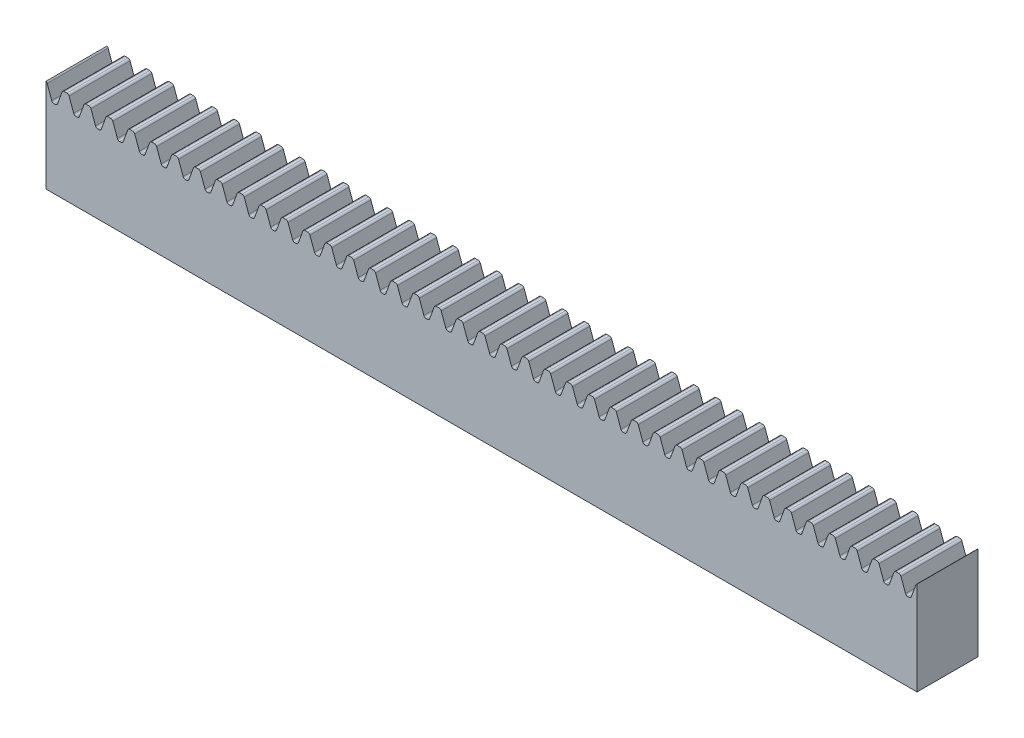
SolidWorks part; units mm, degrees
ref_plane "Front Plane" through (0, 0, 0) normal (0, 0, 1) x (1, 0, 0)
ref_plane "Top Plane" through (0, 0, 0) normal (0, 1, 0) x (1, 0, 0)
ref_plane "Right Plane" through (0, 0, 0) normal (1, 0, 0) x (0, 0, -1)
sketch "Sketch1" plane through (0, 0, 0) normal (0, 0, 1) x (1, 0, 0)
  line L0 (-50, 6.15) -> (-50, -6.15) construction
  line L1 (-50, -6.15) -> (50, -6.15) construction
  line L2 (50, -6.15) -> (50, 6.15) construction
  line L4 (0, 6.15) -> (0, -6.15) construction
  line L5 (-50, 5.35) -> (50, 5.35) construction
  line L6 (-48.0894, 6.15) -> (-47.4151, 6.15) construction
  line L7 (-47.4151, 6.15) -> (-46.7599, 4.35) construction
  line L8 (-48.0894, 6.15) -> (-48.7445, 4.35) construction
  line L9 (-48.7445, 4.35) -> (-46.7599, 4.35) construction
  line L10 (-47.7522, 6.15) -> (-47.7522, 4.35) construction
  line L11 (-50, 0) -> (-42.7257, 0) construction
  line L12 (50, 0) -> (42.7257, 0) construction
  point P15 (-45.2389, 6.15)
  point P16 (-19.5, -6.15)
  point P17 (-47.1239, 5.35)
  point P18 (-48.3805, 5.35)
  point P21 (-0.4, -6.15)
  dimension "Length" = 100
  dimension "Height" = 12.3
  dimension "Approximate Number of Teeth" = 39
  dimension "Pressure Angle" = 20
  dimension "Circular Pitch" = 2.5133
  dimension "Addendum" = 0.8
  dimension "Dedendum" = 1
  dimension "Circular Tooth Thickness" = 1.2566
  dimension "Module" = 0.8
  dimension "Rack Length" = 95.5044
  dimension "D1" = 5.0265
sketch "Sketch2" plane through (0, 0, 0) normal (1, 0, 0) x (0, 0, -1)
  line L0 (-4, 0) -> (4, 0) construction
  dimension "Face Width" = 8
sketch "Sketch3" plane through (0, 0, 0) normal (0, 0, 1) x (1, 0, 0)
  line L1 (-50, 6.15) -> (50, 6.15)
  line L2 (-50, 6.15) -> (-50, -6.15)
  line L3 (-50, -6.15) -> (50, -6.15)
  line L4 (50, 6.15) -> (50, -6.15)
extrude "Boss-Extrude1" add sketch "Sketch3" against normal up to vertex (4 mm away) and the other way up to vertex (4 mm away) up to point (0, 0, -4) other way up to point (0, 0, 4)
sketch "Sketch4" plane through (0, 0, 0) normal (0, 0, 1) x (1, 0, 0)
  line L0 (-47.7522, 6.15) -> (-45.2389, 6.15) construction
  line L9 (-46.4956, 6.15) -> (-46.4956, 4.35)
  line L10 (-46.4956, 4.35) -> (-46.7599, 4.35)
  line L11 (-46.7599, 4.35) -> (-47.4151, 6.15)
  line L12 (-47.4151, 6.15) -> (-46.4956, 6.15)
  line L13 (-48.0894, 6.15) -> (-48.7445, 4.35)
  line L14 (-48.7445, 4.35) -> (-49.0088, 4.35)
  line L15 (-49.0088, 4.35) -> (-49.0088, 6.15)
  line L16 (-49.0088, 6.15) -> (-48.0894, 6.15)
  line L17 (50, 6.15) -> (-50, 6.15) construction
  line L18 (-48.0894, 6.15) -> (-47.9014, 6.15)
  line L19 (-47.603, 6.15) -> (-47.4151, 6.15)
  arc A0 (-48.9324, 4.35) -> (-48.6802, 4.5266) centre (-48.9324, 4.6184) ccw
  arc A1 (-46.8242, 4.5266) -> (-46.572, 4.35) centre (-46.572, 4.6184) ccw
  arc A2 (-48.1536, 5.9734) -> (-47.9014, 6.15) centre (-47.9014, 5.8816) cw
  arc A3 (-47.603, 6.15) -> (-47.3508, 5.9734) centre (-47.603, 5.8816) cw
  dimension "D1" = 0.2684
extrude "Cut-Extrude1" cut sketch "Sketch4" against normal through all both and the other way through all contours L14 A0 L13 L16 L15 | L13 A2 L18 | L19 A3 L11 | L11 A1 L10 L9 L12 region at (-46.8223, 5.4223, 0) region at (-47.4415, 6.1123, 0) region at (-48.0629, 6.1123, 0) region at (-48.6821, 5.4223, 0)
pattern_linear "LPattern1" count 40 spacing 2.5133 along (1, 0, 0) count 2 spacing 2.5133 along (-1, 0, 0) of "Cut-Extrude1"
sketch "Drawing Refernce 1" plane through (0, 0, 4) normal (0, 0, 1) x (1, 0, 0)
  line L0 (-50, 0) -> (50, 0) construction
  point P6 (-35, 0)
  point P7 (-27.5, 0)
  point P8 (35, 0)
  dimension "D1" = 15
  dimension "D2" = 22.5
  dimension "D3" = 15
sketch "Sketch5" plane through (0, -6.15, 0) normal (0, -1, 0) x (1, 0, 0)
  line L1 (-50, 4) -> (50, 4)
  line L2 (-50, 4) -> (-50, -4)
  line L3 (-50, -4) -> (50, -4)
  line L4 (50, 4) -> (50, -4)
extrude "Cut-Extrude2" cut sketch "Sketch5" against normal blind 1.55
sketch "Sketch6" plane through (0, 0, -4) normal (0, 0, -1) x (-1, 0, 0)
  line L162 (-50, -4.6) -> (50, -4.6)
  line L163 (50, -4.6) -> (50, 6.1235)
  line L164 (49.8641, 5.9734) -> (49.3375, 4.5266)
  line L165 (49.0853, 4.35) -> (48.9324, 4.35)
  line L166 (48.6802, 4.5266) -> (48.1536, 5.9734)
  line L167 (47.9014, 6.15) -> (47.603, 6.15)
  line L168 (47.3508, 5.9734) -> (46.8242, 4.5266)
  line L169 (46.572, 4.35) -> (46.4192, 4.35)
  line L170 (46.1669, 4.5266) -> (45.6404, 5.9734)
  line L171 (45.3881, 6.15) -> (45.0897, 6.15)
  line L172 (44.8375, 5.9734) -> (44.3109, 4.5266)
  line L173 (44.0587, 4.35) -> (43.9059, 4.35)
  line L174 (43.6537, 4.5266) -> (43.1271, 5.9734)
  line L175 (42.8749, 6.15) -> (42.5765, 6.15)
  line L176 (42.3242, 5.9734) -> (41.7977, 4.5266)
  line L177 (41.5454, 4.35) -> (41.3926, 4.35)
  line L178 (41.1404, 4.5266) -> (40.6138, 5.9734)
  line L179 (40.3616, 6.15) -> (40.0632, 6.15)
  line L180 (39.811, 5.9734) -> (39.2844, 4.5266)
  line L181 (39.0322, 4.35) -> (38.8793, 4.35)
  line L182 (38.6271, 4.5266) -> (38.1005, 5.9734)
  line L183 (37.8483, 6.15) -> (37.5499, 6.15)
  line L184 (37.2977, 5.9734) -> (36.7711, 4.5266)
  line L185 (36.5189, 4.35) -> (36.3661, 4.35)
  line L186 (36.1138, 4.5266) -> (35.5873, 5.9734)
  line L187 (35.335, 6.15) -> (35.0366, 6.15)
  line L188 (34.7844, 5.9734) -> (34.2578, 4.5266)
  line L189 (34.0056, 4.35) -> (33.8528, 4.35)
  line L190 (33.6006, 4.5266) -> (33.074, 5.9734)
  line L191 (32.8218, 6.15) -> (32.5234, 6.15)
  line L192 (32.2711, 5.9734) -> (31.7446, 4.5266)
  line L193 (31.4923, 4.35) -> (31.3395, 4.35)
  line L194 (31.0873, 4.5266) -> (30.5607, 5.9734)
  line L195 (30.3085, 6.15) -> (30.0101, 6.15)
  line L196 (29.7579, 5.9734) -> (29.2313, 4.5266)
  line L197 (28.9791, 4.35) -> (28.8262, 4.35)
  line L198 (28.574, 4.5266) -> (28.0474, 5.9734)
  line L199 (27.7952, 6.15) -> (27.4968, 6.15)
  line L200 (27.2446, 5.9734) -> (26.718, 4.5266)
  line L201 (26.4658, 4.35) -> (26.313, 4.35)
  line L202 (26.0608, 4.5266) -> (25.5342, 5.9734)
  line L203 (25.2819, 6.15) -> (24.9835, 6.15)
  line L204 (24.7313, 5.9734) -> (24.2047, 4.5266)
  line L205 (23.9525, 4.35) -> (23.7997, 4.35)
  line L206 (23.5475, 4.5266) -> (23.0209, 5.9734)
  line L207 (22.7687, 6.15) -> (22.4703, 6.15)
  line L208 (22.218, 5.9734) -> (21.6915, 4.5266)
  line L209 (21.4392, 4.35) -> (21.2864, 4.35)
  line L210 (21.0342, 4.5266) -> (20.5076, 5.9734)
  line L211 (20.2554, 6.15) -> (19.957, 6.15)
  line L212 (19.7048, 5.9734) -> (19.1782, 4.5266)
  line L213 (18.926, 4.35) -> (18.7731, 4.35)
  line L214 (18.5209, 4.5266) -> (17.9943, 5.9734)
  line L215 (17.7421, 6.15) -> (17.4437, 6.15)
  line L216 (17.1915, 5.9734) -> (16.6649, 4.5266)
  line L217 (16.4127, 4.35) -> (16.2599, 4.35)
  line L218 (16.0077, 4.5266) -> (15.4811, 5.9734)
  line L219 (15.2288, 6.15) -> (14.9304, 6.15)
  line L220 (14.6782, 5.9734) -> (14.1516, 4.5266)
  line L221 (13.8994, 4.35) -> (13.7466, 4.35)
  line L222 (13.4944, 4.5266) -> (12.9678, 5.9734)
  line L223 (12.7156, 6.15) -> (12.4172, 6.15)
  line L224 (12.1649, 5.9734) -> (11.6384, 4.5266)
  line L225 (11.3861, 4.35) -> (11.2333, 4.35)
  line L226 (10.9811, 4.5266) -> (10.4545, 5.9734)
  line L227 (10.2023, 6.15) -> (9.9039, 6.15)
  line L228 (9.6517, 5.9734) -> (9.1251, 4.5266)
  line L229 (8.8729, 4.35) -> (8.72, 4.35)
  line L230 (8.4678, 4.5266) -> (7.9412, 5.9734)
  line L231 (7.689, 6.15) -> (7.3906, 6.15)
  line L232 (7.1384, 5.9734) -> (6.6118, 4.5266)
  line L233 (6.3596, 4.35) -> (6.2068, 4.35)
  line L234 (5.9546, 4.5266) -> (5.428, 5.9734)
  line L235 (5.1758, 6.15) -> (4.8773, 6.15)
  line L236 (4.6251, 5.9734) -> (4.0985, 4.5266)
  line L237 (3.8463, 4.35) -> (3.6935, 4.35)
  line L238 (3.4413, 4.5266) -> (2.9147, 5.9734)
  line L239 (2.6625, 6.15) -> (2.3641, 6.15)
  line L240 (2.1119, 5.9734) -> (1.5853, 4.5266)
  line L241 (1.333, 4.35) -> (1.1802, 4.35)
  line L242 (0.928, 4.5266) -> (0.4014, 5.9734)
  line L243 (0.1492, 6.15) -> (-0.1492, 6.15)
  line L244 (-0.4014, 5.9734) -> (-0.928, 4.5266)
  line L245 (-1.1802, 4.35) -> (-1.333, 4.35)
  line L246 (-1.5853, 4.5266) -> (-2.1119, 5.9734)
  line L247 (-2.3641, 6.15) -> (-2.6625, 6.15)
  line L248 (-2.9147, 5.9734) -> (-3.4413, 4.5266)
  line L249 (-3.6935, 4.35) -> (-3.8463, 4.35)
  line L250 (-4.0985, 4.5266) -> (-4.6251, 5.9734)
  line L251 (-4.8773, 6.15) -> (-5.1758, 6.15)
  line L252 (-5.428, 5.9734) -> (-5.9546, 4.5266)
  line L253 (-6.2068, 4.35) -> (-6.3596, 4.35)
  line L254 (-6.6118, 4.5266) -> (-7.1384, 5.9734)
  line L255 (-7.3906, 6.15) -> (-7.689, 6.15)
  line L256 (-7.9412, 5.9734) -> (-8.4678, 4.5266)
  line L257 (-8.72, 4.35) -> (-8.8729, 4.35)
  line L258 (-9.1251, 4.5266) -> (-9.6517, 5.9734)
  line L259 (-9.9039, 6.15) -> (-10.2023, 6.15)
  line L260 (-10.4545, 5.9734) -> (-10.9811, 4.5266)
  line L261 (-11.2333, 4.35) -> (-11.3861, 4.35)
  line L262 (-11.6384, 4.5266) -> (-12.1649, 5.9734)
  line L263 (-12.4172, 6.15) -> (-12.7156, 6.15)
  line L264 (-12.9678, 5.9734) -> (-13.4944, 4.5266)
  line L265 (-13.7466, 4.35) -> (-13.8994, 4.35)
  line L266 (-14.1516, 4.5266) -> (-14.6782, 5.9734)
  line L267 (-14.9304, 6.15) -> (-15.2288, 6.15)
  line L268 (-15.4811, 5.9734) -> (-16.0077, 4.5266)
  line L269 (-16.2599, 4.35) -> (-16.4127, 4.35)
  line L270 (-16.6649, 4.5266) -> (-17.1915, 5.9734)
  line L271 (-17.4437, 6.15) -> (-17.7421, 6.15)
  line L272 (-17.9943, 5.9734) -> (-18.5209, 4.5266)
  line L273 (-18.7731, 4.35) -> (-18.926, 4.35)
  line L274 (-19.1782, 4.5266) -> (-19.7048, 5.9734)
  line L275 (-19.957, 6.15) -> (-20.2554, 6.15)
  line L276 (-20.5076, 5.9734) -> (-21.0342, 4.5266)
  line L277 (-21.2864, 4.35) -> (-21.4392, 4.35)
  line L278 (-21.6915, 4.5266) -> (-22.218, 5.9734)
  line L279 (-22.4703, 6.15) -> (-22.7687, 6.15)
  line L280 (-23.0209, 5.9734) -> (-23.5475, 4.5266)
  line L281 (-23.7997, 4.35) -> (-23.9525, 4.35)
  line L282 (-24.2047, 4.5266) -> (-24.7313, 5.9734)
  line L283 (-24.9835, 6.15) -> (-25.2819, 6.15)
  line L284 (-25.5342, 5.9734) -> (-26.0608, 4.5266)
  line L285 (-26.313, 4.35) -> (-26.4658, 4.35)
  line L286 (-26.718, 4.5266) -> (-27.2446, 5.9734)
  line L287 (-27.4968, 6.15) -> (-27.7952, 6.15)
  line L288 (-28.0474, 5.9734) -> (-28.574, 4.5266)
  line L289 (-28.8262, 4.35) -> (-28.9791, 4.35)
  line L290 (-29.2313, 4.5266) -> (-29.7579, 5.9734)
  line L291 (-30.0101, 6.15) -> (-30.3085, 6.15)
  line L292 (-30.5607, 5.9734) -> (-31.0873, 4.5266)
  line L293 (-31.3395, 4.35) -> (-31.4923, 4.35)
  line L294 (-31.7446, 4.5266) -> (-32.2711, 5.9734)
  line L295 (-32.5234, 6.15) -> (-32.8218, 6.15)
  line L296 (-33.074, 5.9734) -> (-33.6006, 4.5266)
  line L297 (-33.8528, 4.35) -> (-34.0056, 4.35)
  line L298 (-34.2578, 4.5266) -> (-34.7844, 5.9734)
  line L299 (-35.0366, 6.15) -> (-35.335, 6.15)
  line L300 (-35.5873, 5.9734) -> (-36.1138, 4.5266)
  line L301 (-36.3661, 4.35) -> (-36.5189, 4.35)
  line L302 (-36.7711, 4.5266) -> (-37.2977, 5.9734)
  line L303 (-37.5499, 6.15) -> (-37.8483, 6.15)
  line L304 (-38.1005, 5.9734) -> (-38.6271, 4.5266)
  line L305 (-38.8793, 4.35) -> (-39.0322, 4.35)
  line L306 (-39.2844, 4.5266) -> (-39.811, 5.9734)
  line L307 (-40.0632, 6.15) -> (-40.3616, 6.15)
  line L308 (-40.6138, 5.9734) -> (-41.1404, 4.5266)
  line L309 (-41.3926, 4.35) -> (-41.5454, 4.35)
  line L310 (-41.7977, 4.5266) -> (-42.3242, 5.9734)
  line L311 (-42.5765, 6.15) -> (-42.8749, 6.15)
  line L312 (-43.1271, 5.9734) -> (-43.6537, 4.5266)
  line L313 (-43.9059, 4.35) -> (-44.0587, 4.35)
  line L314 (-44.3109, 4.5266) -> (-44.8375, 5.9734)
  line L315 (-45.0897, 6.15) -> (-45.3881, 6.15)
  line L316 (-45.6404, 5.9734) -> (-46.1669, 4.5266)
  line L317 (-46.4192, 4.35) -> (-46.572, 4.35)
  line L318 (-46.8242, 4.5266) -> (-47.3508, 5.9734)
  line L319 (-47.603, 6.15) -> (-47.9014, 6.15)
  line L320 (-48.1536, 5.9734) -> (-48.6802, 4.5266)
  line L321 (-48.9324, 4.35) -> (-49.0853, 4.35)
  line L322 (-49.3375, 4.5266) -> (-49.8641, 5.9734)
  line L323 (-50, 6.1235) -> (-50, -4.6)
  line L325 (50, -4.6) -> (50, 6.1235)
  line L326 (49.8641, 5.9734) -> (49.3375, 4.5266)
  line L327 (49.0853, 4.35) -> (48.9324, 4.35)
  line L328 (48.6802, 4.5266) -> (48.1536, 5.9734)
  line L329 (47.9014, 6.15) -> (47.603, 6.15)
  line L330 (47.3508, 5.9734) -> (46.8242, 4.5266)
  line L331 (46.572, 4.35) -> (46.4192, 4.35)
  line L332 (46.1669, 4.5266) -> (45.6404, 5.9734)
  line L333 (45.3881, 6.15) -> (45.0897, 6.15)
  line L334 (44.8375, 5.9734) -> (44.3109, 4.5266)
  line L335 (44.0587, 4.35) -> (43.9059, 4.35)
  line L336 (43.6537, 4.5266) -> (43.1271, 5.9734)
  line L337 (42.8749, 6.15) -> (42.5765, 6.15)
  line L338 (42.3242, 5.9734) -> (41.7977, 4.5266)
  line L339 (41.5454, 4.35) -> (41.3926, 4.35)
  line L340 (41.1404, 4.5266) -> (40.6138, 5.9734)
  line L341 (40.3616, 6.15) -> (40.0632, 6.15)
  line L342 (39.811, 5.9734) -> (39.2844, 4.5266)
  line L343 (39.0322, 4.35) -> (38.8793, 4.35)
  line L344 (38.6271, 4.5266) -> (38.1005, 5.9734)
  line L345 (37.8483, 6.15) -> (37.5499, 6.15)
  line L346 (37.2977, 5.9734) -> (36.7711, 4.5266)
  line L347 (36.5189, 4.35) -> (36.3661, 4.35)
  line L348 (36.1138, 4.5266) -> (35.5873, 5.9734)
  line L349 (35.335, 6.15) -> (35.0366, 6.15)
  line L350 (34.7844, 5.9734) -> (34.2578, 4.5266)
  line L351 (34.0056, 4.35) -> (33.8528, 4.35)
  line L352 (33.6006, 4.5266) -> (33.074, 5.9734)
  line L353 (32.8218, 6.15) -> (32.5234, 6.15)
  line L354 (32.2711, 5.9734) -> (31.7446, 4.5266)
  line L355 (31.4923, 4.35) -> (31.3395, 4.35)
  line L356 (31.0873, 4.5266) -> (30.5607, 5.9734)
  line L357 (30.3085, 6.15) -> (30.0101, 6.15)
  line L358 (29.7579, 5.9734) -> (29.2313, 4.5266)
  line L359 (28.9791, 4.35) -> (28.8262, 4.35)
  line L360 (28.574, 4.5266) -> (28.0474, 5.9734)
  line L361 (27.7952, 6.15) -> (27.4968, 6.15)
  line L362 (27.2446, 5.9734) -> (26.718, 4.5266)
  line L363 (26.4658, 4.35) -> (26.313, 4.35)
  line L364 (26.0608, 4.5266) -> (25.5342, 5.9734)
  line L365 (25.2819, 6.15) -> (24.9835, 6.15)
  line L366 (24.7313, 5.9734) -> (24.2047, 4.5266)
  line L367 (23.9525, 4.35) -> (23.7997, 4.35)
  line L368 (23.5475, 4.5266) -> (23.0209, 5.9734)
  line L369 (22.7687, 6.15) -> (22.4703, 6.15)
  line L370 (22.218, 5.9734) -> (21.6915, 4.5266)
  line L371 (21.4392, 4.35) -> (21.2864, 4.35)
  line L372 (21.0342, 4.5266) -> (20.5076, 5.9734)
  line L373 (20.2554, 6.15) -> (19.957, 6.15)
  line L374 (19.7048, 5.9734) -> (19.1782, 4.5266)
  line L375 (18.926, 4.35) -> (18.7731, 4.35)
  line L376 (18.5209, 4.5266) -> (17.9943, 5.9734)
  line L377 (17.7421, 6.15) -> (17.4437, 6.15)
  line L378 (17.1915, 5.9734) -> (16.6649, 4.5266)
  line L379 (16.4127, 4.35) -> (16.2599, 4.35)
  line L380 (16.0077, 4.5266) -> (15.4811, 5.9734)
  line L381 (15.2288, 6.15) -> (14.9304, 6.15)
  line L382 (14.6782, 5.9734) -> (14.1516, 4.5266)
  line L383 (13.8994, 4.35) -> (13.7466, 4.35)
  line L384 (13.4944, 4.5266) -> (12.9678, 5.9734)
  line L385 (12.7156, 6.15) -> (12.4172, 6.15)
  line L386 (12.1649, 5.9734) -> (11.6384, 4.5266)
  line L387 (11.3861, 4.35) -> (11.2333, 4.35)
  line L388 (10.9811, 4.5266) -> (10.4545, 5.9734)
  line L389 (10.2023, 6.15) -> (9.9039, 6.15)
  line L390 (9.6517, 5.9734) -> (9.1251, 4.5266)
  line L391 (8.8729, 4.35) -> (8.72, 4.35)
  line L392 (8.4678, 4.5266) -> (7.9412, 5.9734)
  line L393 (7.689, 6.15) -> (7.3906, 6.15)
  line L394 (7.1384, 5.9734) -> (6.6118, 4.5266)
  line L395 (6.3596, 4.35) -> (6.2068, 4.35)
  line L396 (5.9546, 4.5266) -> (5.428, 5.9734)
  line L397 (5.1758, 6.15) -> (4.8773, 6.15)
  line L398 (4.6251, 5.9734) -> (4.0985, 4.5266)
  line L399 (3.8463, 4.35) -> (3.6935, 4.35)
  line L400 (3.4413, 4.5266) -> (2.9147, 5.9734)
  line L401 (2.6625, 6.15) -> (2.3641, 6.15)
  line L402 (2.1119, 5.9734) -> (1.5853, 4.5266)
  line L403 (1.333, 4.35) -> (1.1802, 4.35)
  line L404 (0.928, 4.5266) -> (0.4014, 5.9734)
  line L405 (0.1492, 6.15) -> (-0.1492, 6.15)
  line L406 (-0.4014, 5.9734) -> (-0.928, 4.5266)
  line L407 (-1.1802, 4.35) -> (-1.333, 4.35)
  line L408 (-1.5853, 4.5266) -> (-2.1119, 5.9734)
  line L409 (-2.3641, 6.15) -> (-2.6625, 6.15)
  line L410 (-2.9147, 5.9734) -> (-3.4413, 4.5266)
  line L411 (-3.6935, 4.35) -> (-3.8463, 4.35)
  line L412 (-4.0985, 4.5266) -> (-4.6251, 5.9734)
  line L413 (-4.8773, 6.15) -> (-5.1758, 6.15)
  line L414 (-5.428, 5.9734) -> (-5.9546, 4.5266)
  line L415 (-6.2068, 4.35) -> (-6.3596, 4.35)
  line L416 (-6.6118, 4.5266) -> (-7.1384, 5.9734)
  line L417 (-7.3906, 6.15) -> (-7.689, 6.15)
  line L418 (-7.9412, 5.9734) -> (-8.4678, 4.5266)
  line L419 (-8.72, 4.35) -> (-8.8729, 4.35)
  line L420 (-9.1251, 4.5266) -> (-9.6517, 5.9734)
  line L421 (-9.9039, 6.15) -> (-10.2023, 6.15)
  line L422 (-10.4545, 5.9734) -> (-10.9811, 4.5266)
  line L423 (-11.2333, 4.35) -> (-11.3861, 4.35)
  line L424 (-11.6384, 4.5266) -> (-12.1649, 5.9734)
  line L425 (-12.4172, 6.15) -> (-12.7156, 6.15)
  line L426 (-12.9678, 5.9734) -> (-13.4944, 4.5266)
  line L427 (-13.7466, 4.35) -> (-13.8994, 4.35)
  line L428 (-14.1516, 4.5266) -> (-14.6782, 5.9734)
  line L429 (-14.9304, 6.15) -> (-15.2288, 6.15)
  line L430 (-15.4811, 5.9734) -> (-16.0077, 4.5266)
  line L431 (-16.2599, 4.35) -> (-16.4127, 4.35)
  line L432 (-16.6649, 4.5266) -> (-17.1915, 5.9734)
  line L433 (-17.4437, 6.15) -> (-17.7421, 6.15)
  line L434 (-17.9943, 5.9734) -> (-18.5209, 4.5266)
  line L435 (-18.7731, 4.35) -> (-18.926, 4.35)
  line L436 (-19.1782, 4.5266) -> (-19.7048, 5.9734)
  line L437 (-19.957, 6.15) -> (-20.2554, 6.15)
  line L438 (-20.5076, 5.9734) -> (-21.0342, 4.5266)
  line L439 (-21.2864, 4.35) -> (-21.4392, 4.35)
  line L440 (-21.6915, 4.5266) -> (-22.218, 5.9734)
  line L441 (-22.4703, 6.15) -> (-22.7687, 6.15)
  line L442 (-23.0209, 5.9734) -> (-23.5475, 4.5266)
  line L443 (-23.7997, 4.35) -> (-23.9525, 4.35)
  line L444 (-24.2047, 4.5266) -> (-24.7313, 5.9734)
  line L445 (-24.9835, 6.15) -> (-25.2819, 6.15)
  line L446 (-25.5342, 5.9734) -> (-26.0608, 4.5266)
  line L447 (-26.313, 4.35) -> (-26.4658, 4.35)
  line L448 (-26.718, 4.5266) -> (-27.2446, 5.9734)
  line L449 (-27.4968, 6.15) -> (-27.7952, 6.15)
  line L450 (-28.0474, 5.9734) -> (-28.574, 4.5266)
  line L451 (-28.8262, 4.35) -> (-28.9791, 4.35)
  line L452 (-29.2313, 4.5266) -> (-29.7579, 5.9734)
  line L453 (-30.0101, 6.15) -> (-30.3085, 6.15)
  line L454 (-30.5607, 5.9734) -> (-31.0873, 4.5266)
  line L455 (-31.3395, 4.35) -> (-31.4923, 4.35)
  line L456 (-31.7446, 4.5266) -> (-32.2711, 5.9734)
  line L457 (-32.5234, 6.15) -> (-32.8218, 6.15)
  line L458 (-33.074, 5.9734) -> (-33.6006, 4.5266)
  line L459 (-33.8528, 4.35) -> (-34.0056, 4.35)
  line L460 (-34.2578, 4.5266) -> (-34.7844, 5.9734)
  line L461 (-35.0366, 6.15) -> (-35.335, 6.15)
  line L462 (-35.5873, 5.9734) -> (-36.1138, 4.5266)
  line L463 (-36.3661, 4.35) -> (-36.5189, 4.35)
  line L464 (-36.7711, 4.5266) -> (-37.2977, 5.9734)
  line L465 (-37.5499, 6.15) -> (-37.8483, 6.15)
  line L466 (-38.1005, 5.9734) -> (-38.6271, 4.5266)
  line L467 (-38.8793, 4.35) -> (-39.0322, 4.35)
  line L468 (-39.2844, 4.5266) -> (-39.811, 5.9734)
  line L469 (-40.0632, 6.15) -> (-40.3616, 6.15)
  line L470 (-40.6138, 5.9734) -> (-41.1404, 4.5266)
  line L471 (-41.3926, 4.35) -> (-41.5454, 4.35)
  line L472 (-41.7977, 4.5266) -> (-42.3242, 5.9734)
  line L473 (-42.5765, 6.15) -> (-42.8749, 6.15)
  line L474 (-43.1271, 5.9734) -> (-43.6537, 4.5266)
  line L475 (-43.9059, 4.35) -> (-44.0587, 4.35)
  line L476 (-44.3109, 4.5266) -> (-44.8375, 5.9734)
  line L477 (-45.0897, 6.15) -> (-45.3881, 6.15)
  line L478 (-45.6404, 5.9734) -> (-46.1669, 4.5266)
  line L479 (-46.4192, 4.35) -> (-46.572, 4.35)
  line L480 (-46.8242, 4.5266) -> (-47.3508, 5.9734)
  line L481 (-47.603, 6.15) -> (-47.9014, 6.15)
  line L482 (-48.1536, 5.9734) -> (-48.6802, 4.5266)
  line L483 (-48.9324, 4.35) -> (-49.0853, 4.35)
  line L484 (-49.3375, 4.5266) -> (-49.8641, 5.9734)
  line L485 (-50, 6.1235) -> (-50, -4.6)
  line L487 (-50, -4.6) -> (50, -4.6)
  arc A160 (50, 6.1235) -> (49.8641, 5.9734) centre (50.1163, 5.8816) ccw
  arc A161 (49.0853, 4.35) -> (49.3375, 4.5266) centre (49.0853, 4.6184) ccw
  arc A162 (48.6802, 4.5266) -> (48.9324, 4.35) centre (48.9324, 4.6184) ccw
  arc A163 (48.1536, 5.9734) -> (47.9014, 6.15) centre (47.9014, 5.8816) ccw
  arc A164 (47.603, 6.15) -> (47.3508, 5.9734) centre (47.603, 5.8816) ccw
  arc A165 (46.572, 4.35) -> (46.8242, 4.5266) centre (46.572, 4.6184) ccw
  arc A166 (46.1669, 4.5266) -> (46.4192, 4.35) centre (46.4192, 4.6184) ccw
  arc A167 (45.6404, 5.9734) -> (45.3881, 6.15) centre (45.3881, 5.8816) ccw
  arc A168 (45.0897, 6.15) -> (44.8375, 5.9734) centre (45.0897, 5.8816) ccw
  arc A169 (44.0587, 4.35) -> (44.3109, 4.5266) centre (44.0587, 4.6184) ccw
  arc A170 (43.6537, 4.5266) -> (43.9059, 4.35) centre (43.9059, 4.6184) ccw
  arc A171 (43.1271, 5.9734) -> (42.8749, 6.15) centre (42.8749, 5.8816) ccw
  arc A172 (42.5765, 6.15) -> (42.3242, 5.9734) centre (42.5765, 5.8816) ccw
  arc A173 (41.5454, 4.35) -> (41.7977, 4.5266) centre (41.5454, 4.6184) ccw
  arc A174 (41.1404, 4.5266) -> (41.3926, 4.35) centre (41.3926, 4.6184) ccw
  arc A175 (40.6138, 5.9734) -> (40.3616, 6.15) centre (40.3616, 5.8816) ccw
  arc A176 (40.0632, 6.15) -> (39.811, 5.9734) centre (40.0632, 5.8816) ccw
  arc A177 (39.0322, 4.35) -> (39.2844, 4.5266) centre (39.0322, 4.6184) ccw
  arc A178 (38.6271, 4.5266) -> (38.8793, 4.35) centre (38.8793, 4.6184) ccw
  arc A179 (38.1005, 5.9734) -> (37.8483, 6.15) centre (37.8483, 5.8816) ccw
  arc A180 (37.5499, 6.15) -> (37.2977, 5.9734) centre (37.5499, 5.8816) ccw
  arc A181 (36.5189, 4.35) -> (36.7711, 4.5266) centre (36.5189, 4.6184) ccw
  arc A182 (36.1138, 4.5266) -> (36.3661, 4.35) centre (36.3661, 4.6184) ccw
  arc A183 (35.5873, 5.9734) -> (35.335, 6.15) centre (35.335, 5.8816) ccw
  arc A184 (35.0366, 6.15) -> (34.7844, 5.9734) centre (35.0366, 5.8816) ccw
  arc A185 (34.0056, 4.35) -> (34.2578, 4.5266) centre (34.0056, 4.6184) ccw
  arc A186 (33.6006, 4.5266) -> (33.8528, 4.35) centre (33.8528, 4.6184) ccw
  arc A187 (33.074, 5.9734) -> (32.8218, 6.15) centre (32.8218, 5.8816) ccw
  arc A188 (32.5234, 6.15) -> (32.2711, 5.9734) centre (32.5234, 5.8816) ccw
  arc A189 (31.4923, 4.35) -> (31.7446, 4.5266) centre (31.4923, 4.6184) ccw
  arc A190 (31.0873, 4.5266) -> (31.3395, 4.35) centre (31.3395, 4.6184) ccw
  arc A191 (30.5607, 5.9734) -> (30.3085, 6.15) centre (30.3085, 5.8816) ccw
  arc A192 (30.0101, 6.15) -> (29.7579, 5.9734) centre (30.0101, 5.8816) ccw
  arc A193 (28.9791, 4.35) -> (29.2313, 4.5266) centre (28.9791, 4.6184) ccw
  arc A194 (28.574, 4.5266) -> (28.8262, 4.35) centre (28.8262, 4.6184) ccw
  arc A195 (28.0474, 5.9734) -> (27.7952, 6.15) centre (27.7952, 5.8816) ccw
  arc A196 (27.4968, 6.15) -> (27.2446, 5.9734) centre (27.4968, 5.8816) ccw
  arc A197 (26.4658, 4.35) -> (26.718, 4.5266) centre (26.4658, 4.6184) ccw
  arc A198 (26.0608, 4.5266) -> (26.313, 4.35) centre (26.313, 4.6184) ccw
  arc A199 (25.5342, 5.9734) -> (25.2819, 6.15) centre (25.2819, 5.8816) ccw
  arc A200 (24.9835, 6.15) -> (24.7313, 5.9734) centre (24.9835, 5.8816) ccw
  arc A201 (23.9525, 4.35) -> (24.2047, 4.5266) centre (23.9525, 4.6184) ccw
  arc A202 (23.5475, 4.5266) -> (23.7997, 4.35) centre (23.7997, 4.6184) ccw
  arc A203 (23.0209, 5.9734) -> (22.7687, 6.15) centre (22.7687, 5.8816) ccw
  arc A204 (22.4703, 6.15) -> (22.218, 5.9734) centre (22.4703, 5.8816) ccw
  arc A205 (21.4392, 4.35) -> (21.6915, 4.5266) centre (21.4392, 4.6184) ccw
  arc A206 (21.0342, 4.5266) -> (21.2864, 4.35) centre (21.2864, 4.6184) ccw
  arc A207 (20.5076, 5.9734) -> (20.2554, 6.15) centre (20.2554, 5.8816) ccw
  arc A208 (19.957, 6.15) -> (19.7048, 5.9734) centre (19.957, 5.8816) ccw
  arc A209 (18.926, 4.35) -> (19.1782, 4.5266) centre (18.926, 4.6184) ccw
  arc A210 (18.5209, 4.5266) -> (18.7731, 4.35) centre (18.7731, 4.6184) ccw
  arc A211 (17.9943, 5.9734) -> (17.7421, 6.15) centre (17.7421, 5.8816) ccw
  arc A212 (17.4437, 6.15) -> (17.1915, 5.9734) centre (17.4437, 5.8816) ccw
  arc A213 (16.4127, 4.35) -> (16.6649, 4.5266) centre (16.4127, 4.6184) ccw
  arc A214 (16.0077, 4.5266) -> (16.2599, 4.35) centre (16.2599, 4.6184) ccw
  arc A215 (15.4811, 5.9734) -> (15.2288, 6.15) centre (15.2288, 5.8816) ccw
  arc A216 (14.9304, 6.15) -> (14.6782, 5.9734) centre (14.9304, 5.8816) ccw
  arc A217 (13.8994, 4.35) -> (14.1516, 4.5266) centre (13.8994, 4.6184) ccw
  arc A218 (13.4944, 4.5266) -> (13.7466, 4.35) centre (13.7466, 4.6184) ccw
  arc A219 (12.9678, 5.9734) -> (12.7156, 6.15) centre (12.7156, 5.8816) ccw
  arc A220 (12.4172, 6.15) -> (12.1649, 5.9734) centre (12.4172, 5.8816) ccw
  arc A221 (11.3861, 4.35) -> (11.6384, 4.5266) centre (11.3861, 4.6184) ccw
  arc A222 (10.9811, 4.5266) -> (11.2333, 4.35) centre (11.2333, 4.6184) ccw
  arc A223 (10.4545, 5.9734) -> (10.2023, 6.15) centre (10.2023, 5.8816) ccw
  arc A224 (9.9039, 6.15) -> (9.6517, 5.9734) centre (9.9039, 5.8816) ccw
  arc A225 (8.8729, 4.35) -> (9.1251, 4.5266) centre (8.8729, 4.6184) ccw
  arc A226 (8.4678, 4.5266) -> (8.72, 4.35) centre (8.72, 4.6184) ccw
  arc A227 (7.9412, 5.9734) -> (7.689, 6.15) centre (7.689, 5.8816) ccw
  arc A228 (7.3906, 6.15) -> (7.1384, 5.9734) centre (7.3906, 5.8816) ccw
  arc A229 (6.3596, 4.35) -> (6.6118, 4.5266) centre (6.3596, 4.6184) ccw
  arc A230 (5.9546, 4.5266) -> (6.2068, 4.35) centre (6.2068, 4.6184) ccw
  arc A231 (5.428, 5.9734) -> (5.1758, 6.15) centre (5.1758, 5.8816) ccw
  arc A232 (4.8773, 6.15) -> (4.6251, 5.9734) centre (4.8773, 5.8816) ccw
  arc A233 (3.8463, 4.35) -> (4.0985, 4.5266) centre (3.8463, 4.6184) ccw
  arc A234 (3.4413, 4.5266) -> (3.6935, 4.35) centre (3.6935, 4.6184) ccw
  arc A235 (2.9147, 5.9734) -> (2.6625, 6.15) centre (2.6625, 5.8816) ccw
  arc A236 (2.3641, 6.15) -> (2.1119, 5.9734) centre (2.3641, 5.8816) ccw
  arc A237 (1.333, 4.35) -> (1.5853, 4.5266) centre (1.333, 4.6184) ccw
  arc A238 (0.928, 4.5266) -> (1.1802, 4.35) centre (1.1802, 4.6184) ccw
  arc A239 (0.4014, 5.9734) -> (0.1492, 6.15) centre (0.1492, 5.8816) ccw
  arc A240 (-0.1492, 6.15) -> (-0.4014, 5.9734) centre (-0.1492, 5.8816) ccw
  arc A241 (-1.1802, 4.35) -> (-0.928, 4.5266) centre (-1.1802, 4.6184) ccw
  arc A242 (-1.5853, 4.5266) -> (-1.333, 4.35) centre (-1.333, 4.6184) ccw
  arc A243 (-2.1119, 5.9734) -> (-2.3641, 6.15) centre (-2.3641, 5.8816) ccw
  arc A244 (-2.6625, 6.15) -> (-2.9147, 5.9734) centre (-2.6625, 5.8816) ccw
  arc A245 (-3.6935, 4.35) -> (-3.4413, 4.5266) centre (-3.6935, 4.6184) ccw
  arc A246 (-4.0985, 4.5266) -> (-3.8463, 4.35) centre (-3.8463, 4.6184) ccw
  arc A247 (-4.6251, 5.9734) -> (-4.8773, 6.15) centre (-4.8773, 5.8816) ccw
  arc A248 (-5.1758, 6.15) -> (-5.428, 5.9734) centre (-5.1758, 5.8816) ccw
  arc A249 (-6.2068, 4.35) -> (-5.9546, 4.5266) centre (-6.2068, 4.6184) ccw
  arc A250 (-6.6118, 4.5266) -> (-6.3596, 4.35) centre (-6.3596, 4.6184) ccw
  arc A251 (-7.1384, 5.9734) -> (-7.3906, 6.15) centre (-7.3906, 5.8816) ccw
  arc A252 (-7.689, 6.15) -> (-7.9412, 5.9734) centre (-7.689, 5.8816) ccw
  arc A253 (-8.72, 4.35) -> (-8.4678, 4.5266) centre (-8.72, 4.6184) ccw
  arc A254 (-9.1251, 4.5266) -> (-8.8729, 4.35) centre (-8.8729, 4.6184) ccw
  arc A255 (-9.6517, 5.9734) -> (-9.9039, 6.15) centre (-9.9039, 5.8816) ccw
  arc A256 (-10.2023, 6.15) -> (-10.4545, 5.9734) centre (-10.2023, 5.8816) ccw
  arc A257 (-11.2333, 4.35) -> (-10.9811, 4.5266) centre (-11.2333, 4.6184) ccw
  arc A258 (-11.6384, 4.5266) -> (-11.3861, 4.35) centre (-11.3861, 4.6184) ccw
  arc A259 (-12.1649, 5.9734) -> (-12.4172, 6.15) centre (-12.4172, 5.8816) ccw
  arc A260 (-12.7156, 6.15) -> (-12.9678, 5.9734) centre (-12.7156, 5.8816) ccw
  arc A261 (-13.7466, 4.35) -> (-13.4944, 4.5266) centre (-13.7466, 4.6184) ccw
  arc A262 (-14.1516, 4.5266) -> (-13.8994, 4.35) centre (-13.8994, 4.6184) ccw
  arc A263 (-14.6782, 5.9734) -> (-14.9304, 6.15) centre (-14.9304, 5.8816) ccw
  arc A264 (-15.2288, 6.15) -> (-15.4811, 5.9734) centre (-15.2288, 5.8816) ccw
  arc A265 (-16.2599, 4.35) -> (-16.0077, 4.5266) centre (-16.2599, 4.6184) ccw
  arc A266 (-16.6649, 4.5266) -> (-16.4127, 4.35) centre (-16.4127, 4.6184) ccw
  arc A267 (-17.1915, 5.9734) -> (-17.4437, 6.15) centre (-17.4437, 5.8816) ccw
  arc A268 (-17.7421, 6.15) -> (-17.9943, 5.9734) centre (-17.7421, 5.8816) ccw
  arc A269 (-18.7731, 4.35) -> (-18.5209, 4.5266) centre (-18.7731, 4.6184) ccw
  arc A270 (-19.1782, 4.5266) -> (-18.926, 4.35) centre (-18.926, 4.6184) ccw
  arc A271 (-19.7048, 5.9734) -> (-19.957, 6.15) centre (-19.957, 5.8816) ccw
  arc A272 (-20.2554, 6.15) -> (-20.5076, 5.9734) centre (-20.2554, 5.8816) ccw
  arc A273 (-21.2864, 4.35) -> (-21.0342, 4.5266) centre (-21.2864, 4.6184) ccw
  arc A274 (-21.6915, 4.5266) -> (-21.4392, 4.35) centre (-21.4392, 4.6184) ccw
  arc A275 (-22.218, 5.9734) -> (-22.4703, 6.15) centre (-22.4703, 5.8816) ccw
  arc A276 (-22.7687, 6.15) -> (-23.0209, 5.9734) centre (-22.7687, 5.8816) ccw
  arc A277 (-23.7997, 4.35) -> (-23.5475, 4.5266) centre (-23.7997, 4.6184) ccw
  arc A278 (-24.2047, 4.5266) -> (-23.9525, 4.35) centre (-23.9525, 4.6184) ccw
  arc A279 (-24.7313, 5.9734) -> (-24.9835, 6.15) centre (-24.9835, 5.8816) ccw
  arc A280 (-25.2819, 6.15) -> (-25.5342, 5.9734) centre (-25.2819, 5.8816) ccw
  arc A281 (-26.313, 4.35) -> (-26.0608, 4.5266) centre (-26.313, 4.6184) ccw
  arc A282 (-26.718, 4.5266) -> (-26.4658, 4.35) centre (-26.4658, 4.6184) ccw
  arc A283 (-27.2446, 5.9734) -> (-27.4968, 6.15) centre (-27.4968, 5.8816) ccw
  arc A284 (-27.7952, 6.15) -> (-28.0474, 5.9734) centre (-27.7952, 5.8816) ccw
  arc A285 (-28.8262, 4.35) -> (-28.574, 4.5266) centre (-28.8262, 4.6184) ccw
  arc A286 (-29.2313, 4.5266) -> (-28.9791, 4.35) centre (-28.9791, 4.6184) ccw
  arc A287 (-29.7579, 5.9734) -> (-30.0101, 6.15) centre (-30.0101, 5.8816) ccw
  arc A288 (-30.3085, 6.15) -> (-30.5607, 5.9734) centre (-30.3085, 5.8816) ccw
  arc A289 (-31.3395, 4.35) -> (-31.0873, 4.5266) centre (-31.3395, 4.6184) ccw
  arc A290 (-31.7446, 4.5266) -> (-31.4923, 4.35) centre (-31.4923, 4.6184) ccw
  arc A291 (-32.2711, 5.9734) -> (-32.5234, 6.15) centre (-32.5234, 5.8816) ccw
  arc A292 (-32.8218, 6.15) -> (-33.074, 5.9734) centre (-32.8218, 5.8816) ccw
  arc A293 (-33.8528, 4.35) -> (-33.6006, 4.5266) centre (-33.8528, 4.6184) ccw
  arc A294 (-34.2578, 4.5266) -> (-34.0056, 4.35) centre (-34.0056, 4.6184) ccw
  arc A295 (-34.7844, 5.9734) -> (-35.0366, 6.15) centre (-35.0366, 5.8816) ccw
  arc A296 (-35.335, 6.15) -> (-35.5873, 5.9734) centre (-35.335, 5.8816) ccw
  arc A297 (-36.3661, 4.35) -> (-36.1138, 4.5266) centre (-36.3661, 4.6184) ccw
  arc A298 (-36.7711, 4.5266) -> (-36.5189, 4.35) centre (-36.5189, 4.6184) ccw
  arc A299 (-37.2977, 5.9734) -> (-37.5499, 6.15) centre (-37.5499, 5.8816) ccw
  arc A300 (-37.8483, 6.15) -> (-38.1005, 5.9734) centre (-37.8483, 5.8816) ccw
  arc A301 (-38.8793, 4.35) -> (-38.6271, 4.5266) centre (-38.8793, 4.6184) ccw
  arc A302 (-39.2844, 4.5266) -> (-39.0322, 4.35) centre (-39.0322, 4.6184) ccw
  arc A303 (-39.811, 5.9734) -> (-40.0632, 6.15) centre (-40.0632, 5.8816) ccw
  arc A304 (-40.3616, 6.15) -> (-40.6138, 5.9734) centre (-40.3616, 5.8816) ccw
  arc A305 (-41.3926, 4.35) -> (-41.1404, 4.5266) centre (-41.3926, 4.6184) ccw
  arc A306 (-41.7977, 4.5266) -> (-41.5454, 4.35) centre (-41.5454, 4.6184) ccw
  arc A307 (-42.3242, 5.9734) -> (-42.5765, 6.15) centre (-42.5765, 5.8816) ccw
  arc A308 (-42.8749, 6.15) -> (-43.1271, 5.9734) centre (-42.8749, 5.8816) ccw
  arc A309 (-43.9059, 4.35) -> (-43.6537, 4.5266) centre (-43.9059, 4.6184) ccw
  arc A310 (-44.3109, 4.5266) -> (-44.0587, 4.35) centre (-44.0587, 4.6184) ccw
  arc A311 (-44.8375, 5.9734) -> (-45.0897, 6.15) centre (-45.0897, 5.8816) ccw
  arc A312 (-45.3881, 6.15) -> (-45.6404, 5.9734) centre (-45.3881, 5.8816) ccw
  arc A313 (-46.4192, 4.35) -> (-46.1669, 4.5266) centre (-46.4192, 4.6184) ccw
  arc A314 (-46.8242, 4.5266) -> (-46.572, 4.35) centre (-46.572, 4.6184) ccw
  arc A315 (-47.3508, 5.9734) -> (-47.603, 6.15) centre (-47.603, 5.8816) ccw
  arc A316 (-47.9014, 6.15) -> (-48.1536, 5.9734) centre (-47.9014, 5.8816) ccw
  arc A317 (-48.9324, 4.35) -> (-48.6802, 4.5266) centre (-48.9324, 4.6184) ccw
  arc A318 (-49.3375, 4.5266) -> (-49.0853, 4.35) centre (-49.0853, 4.6184) ccw
  arc A319 (-49.8641, 5.9734) -> (-50, 6.1235) centre (-50.1163, 5.8816) ccw
  arc A320 (50, 6.1235) -> (49.8641, 5.9734) centre (50.1163, 5.8816) ccw
  arc A321 (49.0853, 4.35) -> (49.3375, 4.5266) centre (49.0853, 4.6184) ccw
  arc A322 (48.6802, 4.5266) -> (48.9324, 4.35) centre (48.9324, 4.6184) ccw
  arc A323 (48.1536, 5.9734) -> (47.9014, 6.15) centre (47.9014, 5.8816) ccw
  arc A324 (47.603, 6.15) -> (47.3508, 5.9734) centre (47.603, 5.8816) ccw
  arc A325 (46.572, 4.35) -> (46.8242, 4.5266) centre (46.572, 4.6184) ccw
  arc A326 (46.1669, 4.5266) -> (46.4192, 4.35) centre (46.4192, 4.6184) ccw
  arc A327 (45.6404, 5.9734) -> (45.3881, 6.15) centre (45.3881, 5.8816) ccw
  arc A328 (45.0897, 6.15) -> (44.8375, 5.9734) centre (45.0897, 5.8816) ccw
  arc A329 (44.0587, 4.35) -> (44.3109, 4.5266) centre (44.0587, 4.6184) ccw
  arc A330 (43.6537, 4.5266) -> (43.9059, 4.35) centre (43.9059, 4.6184) ccw
  arc A331 (43.1271, 5.9734) -> (42.8749, 6.15) centre (42.8749, 5.8816) ccw
  arc A332 (42.5765, 6.15) -> (42.3242, 5.9734) centre (42.5765, 5.8816) ccw
  arc A333 (41.5454, 4.35) -> (41.7977, 4.5266) centre (41.5454, 4.6184) ccw
  arc A334 (41.1404, 4.5266) -> (41.3926, 4.35) centre (41.3926, 4.6184) ccw
  arc A335 (40.6138, 5.9734) -> (40.3616, 6.15) centre (40.3616, 5.8816) ccw
  arc A336 (40.0632, 6.15) -> (39.811, 5.9734) centre (40.0632, 5.8816) ccw
  arc A337 (39.0322, 4.35) -> (39.2844, 4.5266) centre (39.0322, 4.6184) ccw
  arc A338 (38.6271, 4.5266) -> (38.8793, 4.35) centre (38.8793, 4.6184) ccw
  arc A339 (38.1005, 5.9734) -> (37.8483, 6.15) centre (37.8483, 5.8816) ccw
  arc A340 (37.5499, 6.15) -> (37.2977, 5.9734) centre (37.5499, 5.8816) ccw
  arc A341 (36.5189, 4.35) -> (36.7711, 4.5266) centre (36.5189, 4.6184) ccw
  arc A342 (36.1138, 4.5266) -> (36.3661, 4.35) centre (36.3661, 4.6184) ccw
  arc A343 (35.5873, 5.9734) -> (35.335, 6.15) centre (35.335, 5.8816) ccw
  arc A344 (35.0366, 6.15) -> (34.7844, 5.9734) centre (35.0366, 5.8816) ccw
  arc A345 (34.0056, 4.35) -> (34.2578, 4.5266) centre (34.0056, 4.6184) ccw
  arc A346 (33.6006, 4.5266) -> (33.8528, 4.35) centre (33.8528, 4.6184) ccw
  arc A347 (33.074, 5.9734) -> (32.8218, 6.15) centre (32.8218, 5.8816) ccw
  arc A348 (32.5234, 6.15) -> (32.2711, 5.9734) centre (32.5234, 5.8816) ccw
  arc A349 (31.4923, 4.35) -> (31.7446, 4.5266) centre (31.4923, 4.6184) ccw
  arc A350 (31.0873, 4.5266) -> (31.3395, 4.35) centre (31.3395, 4.6184) ccw
  arc A351 (30.5607, 5.9734) -> (30.3085, 6.15) centre (30.3085, 5.8816) ccw
  arc A352 (30.0101, 6.15) -> (29.7579, 5.9734) centre (30.0101, 5.8816) ccw
  arc A353 (28.9791, 4.35) -> (29.2313, 4.5266) centre (28.9791, 4.6184) ccw
  arc A354 (28.574, 4.5266) -> (28.8262, 4.35) centre (28.8262, 4.6184) ccw
  arc A355 (28.0474, 5.9734) -> (27.7952, 6.15) centre (27.7952, 5.8816) ccw
  arc A356 (27.4968, 6.15) -> (27.2446, 5.9734) centre (27.4968, 5.8816) ccw
  arc A357 (26.4658, 4.35) -> (26.718, 4.5266) centre (26.4658, 4.6184) ccw
  arc A358 (26.0608, 4.5266) -> (26.313, 4.35) centre (26.313, 4.6184) ccw
  arc A359 (25.5342, 5.9734) -> (25.2819, 6.15) centre (25.2819, 5.8816) ccw
  arc A360 (24.9835, 6.15) -> (24.7313, 5.9734) centre (24.9835, 5.8816) ccw
  arc A361 (23.9525, 4.35) -> (24.2047, 4.5266) centre (23.9525, 4.6184) ccw
  arc A362 (23.5475, 4.5266) -> (23.7997, 4.35) centre (23.7997, 4.6184) ccw
  arc A363 (23.0209, 5.9734) -> (22.7687, 6.15) centre (22.7687, 5.8816) ccw
  arc A364 (22.4703, 6.15) -> (22.218, 5.9734) centre (22.4703, 5.8816) ccw
  arc A365 (21.4392, 4.35) -> (21.6915, 4.5266) centre (21.4392, 4.6184) ccw
  arc A366 (21.0342, 4.5266) -> (21.2864, 4.35) centre (21.2864, 4.6184) ccw
  arc A367 (20.5076, 5.9734) -> (20.2554, 6.15) centre (20.2554, 5.8816) ccw
  arc A368 (19.957, 6.15) -> (19.7048, 5.9734) centre (19.957, 5.8816) ccw
  arc A369 (18.926, 4.35) -> (19.1782, 4.5266) centre (18.926, 4.6184) ccw
  arc A370 (18.5209, 4.5266) -> (18.7731, 4.35) centre (18.7731, 4.6184) ccw
  arc A371 (17.9943, 5.9734) -> (17.7421, 6.15) centre (17.7421, 5.8816) ccw
  arc A372 (17.4437, 6.15) -> (17.1915, 5.9734) centre (17.4437, 5.8816) ccw
  arc A373 (16.4127, 4.35) -> (16.6649, 4.5266) centre (16.4127, 4.6184) ccw
  arc A374 (16.0077, 4.5266) -> (16.2599, 4.35) centre (16.2599, 4.6184) ccw
  arc A375 (15.4811, 5.9734) -> (15.2288, 6.15) centre (15.2288, 5.8816) ccw
  arc A376 (14.9304, 6.15) -> (14.6782, 5.9734) centre (14.9304, 5.8816) ccw
  arc A377 (13.8994, 4.35) -> (14.1516, 4.5266) centre (13.8994, 4.6184) ccw
  arc A378 (13.4944, 4.5266) -> (13.7466, 4.35) centre (13.7466, 4.6184) ccw
  arc A379 (12.9678, 5.9734) -> (12.7156, 6.15) centre (12.7156, 5.8816) ccw
  arc A380 (12.4172, 6.15) -> (12.1649, 5.9734) centre (12.4172, 5.8816) ccw
  arc A381 (11.3861, 4.35) -> (11.6384, 4.5266) centre (11.3861, 4.6184) ccw
  arc A382 (10.9811, 4.5266) -> (11.2333, 4.35) centre (11.2333, 4.6184) ccw
  arc A383 (10.4545, 5.9734) -> (10.2023, 6.15) centre (10.2023, 5.8816) ccw
  arc A384 (9.9039, 6.15) -> (9.6517, 5.9734) centre (9.9039, 5.8816) ccw
  arc A385 (8.8729, 4.35) -> (9.1251, 4.5266) centre (8.8729, 4.6184) ccw
  arc A386 (8.4678, 4.5266) -> (8.72, 4.35) centre (8.72, 4.6184) ccw
  arc A387 (7.9412, 5.9734) -> (7.689, 6.15) centre (7.689, 5.8816) ccw
  arc A388 (7.3906, 6.15) -> (7.1384, 5.9734) centre (7.3906, 5.8816) ccw
  arc A389 (6.3596, 4.35) -> (6.6118, 4.5266) centre (6.3596, 4.6184) ccw
  arc A390 (5.9546, 4.5266) -> (6.2068, 4.35) centre (6.2068, 4.6184) ccw
  arc A391 (5.428, 5.9734) -> (5.1758, 6.15) centre (5.1758, 5.8816) ccw
  arc A392 (4.8773, 6.15) -> (4.6251, 5.9734) centre (4.8773, 5.8816) ccw
  arc A393 (3.8463, 4.35) -> (4.0985, 4.5266) centre (3.8463, 4.6184) ccw
  arc A394 (3.4413, 4.5266) -> (3.6935, 4.35) centre (3.6935, 4.6184) ccw
  arc A395 (2.9147, 5.9734) -> (2.6625, 6.15) centre (2.6625, 5.8816) ccw
  arc A396 (2.3641, 6.15) -> (2.1119, 5.9734) centre (2.3641, 5.8816) ccw
  arc A397 (1.333, 4.35) -> (1.5853, 4.5266) centre (1.333, 4.6184) ccw
  arc A398 (0.928, 4.5266) -> (1.1802, 4.35) centre (1.1802, 4.6184) ccw
  arc A399 (0.4014, 5.9734) -> (0.1492, 6.15) centre (0.1492, 5.8816) ccw
  arc A400 (-0.1492, 6.15) -> (-0.4014, 5.9734) centre (-0.1492, 5.8816) ccw
  arc A401 (-1.1802, 4.35) -> (-0.928, 4.5266) centre (-1.1802, 4.6184) ccw
  arc A402 (-1.5853, 4.5266) -> (-1.333, 4.35) centre (-1.333, 4.6184) ccw
  arc A403 (-2.1119, 5.9734) -> (-2.3641, 6.15) centre (-2.3641, 5.8816) ccw
  arc A404 (-2.6625, 6.15) -> (-2.9147, 5.9734) centre (-2.6625, 5.8816) ccw
  arc A405 (-3.6935, 4.35) -> (-3.4413, 4.5266) centre (-3.6935, 4.6184) ccw
  arc A406 (-4.0985, 4.5266) -> (-3.8463, 4.35) centre (-3.8463, 4.6184) ccw
  arc A407 (-4.6251, 5.9734) -> (-4.8773, 6.15) centre (-4.8773, 5.8816) ccw
  arc A408 (-5.1758, 6.15) -> (-5.428, 5.9734) centre (-5.1758, 5.8816) ccw
  arc A409 (-6.2068, 4.35) -> (-5.9546, 4.5266) centre (-6.2068, 4.6184) ccw
  arc A410 (-6.6118, 4.5266) -> (-6.3596, 4.35) centre (-6.3596, 4.6184) ccw
  arc A411 (-7.1384, 5.9734) -> (-7.3906, 6.15) centre (-7.3906, 5.8816) ccw
  arc A412 (-7.689, 6.15) -> (-7.9412, 5.9734) centre (-7.689, 5.8816) ccw
  arc A413 (-8.72, 4.35) -> (-8.4678, 4.5266) centre (-8.72, 4.6184) ccw
  arc A414 (-9.1251, 4.5266) -> (-8.8729, 4.35) centre (-8.8729, 4.6184) ccw
  arc A415 (-9.6517, 5.9734) -> (-9.9039, 6.15) centre (-9.9039, 5.8816) ccw
  arc A416 (-10.2023, 6.15) -> (-10.4545, 5.9734) centre (-10.2023, 5.8816) ccw
  arc A417 (-11.2333, 4.35) -> (-10.9811, 4.5266) centre (-11.2333, 4.6184) ccw
  arc A418 (-11.6384, 4.5266) -> (-11.3861, 4.35) centre (-11.3861, 4.6184) ccw
  arc A419 (-12.1649, 5.9734) -> (-12.4172, 6.15) centre (-12.4172, 5.8816) ccw
  arc A420 (-12.7156, 6.15) -> (-12.9678, 5.9734) centre (-12.7156, 5.8816) ccw
  arc A421 (-13.7466, 4.35) -> (-13.4944, 4.5266) centre (-13.7466, 4.6184) ccw
  arc A422 (-14.1516, 4.5266) -> (-13.8994, 4.35) centre (-13.8994, 4.6184) ccw
  arc A423 (-14.6782, 5.9734) -> (-14.9304, 6.15) centre (-14.9304, 5.8816) ccw
  arc A424 (-15.2288, 6.15) -> (-15.4811, 5.9734) centre (-15.2288, 5.8816) ccw
  arc A425 (-16.2599, 4.35) -> (-16.0077, 4.5266) centre (-16.2599, 4.6184) ccw
  arc A426 (-16.6649, 4.5266) -> (-16.4127, 4.35) centre (-16.4127, 4.6184) ccw
  arc A427 (-17.1915, 5.9734) -> (-17.4437, 6.15) centre (-17.4437, 5.8816) ccw
  arc A428 (-17.7421, 6.15) -> (-17.9943, 5.9734) centre (-17.7421, 5.8816) ccw
  arc A429 (-18.7731, 4.35) -> (-18.5209, 4.5266) centre (-18.7731, 4.6184) ccw
  arc A430 (-19.1782, 4.5266) -> (-18.926, 4.35) centre (-18.926, 4.6184) ccw
  arc A431 (-19.7048, 5.9734) -> (-19.957, 6.15) centre (-19.957, 5.8816) ccw
  arc A432 (-20.2554, 6.15) -> (-20.5076, 5.9734) centre (-20.2554, 5.8816) ccw
  arc A433 (-21.2864, 4.35) -> (-21.0342, 4.5266) centre (-21.2864, 4.6184) ccw
  arc A434 (-21.6915, 4.5266) -> (-21.4392, 4.35) centre (-21.4392, 4.6184) ccw
  arc A435 (-22.218, 5.9734) -> (-22.4703, 6.15) centre (-22.4703, 5.8816) ccw
  arc A436 (-22.7687, 6.15) -> (-23.0209, 5.9734) centre (-22.7687, 5.8816) ccw
  arc A437 (-23.7997, 4.35) -> (-23.5475, 4.5266) centre (-23.7997, 4.6184) ccw
  arc A438 (-24.2047, 4.5266) -> (-23.9525, 4.35) centre (-23.9525, 4.6184) ccw
  arc A439 (-24.7313, 5.9734) -> (-24.9835, 6.15) centre (-24.9835, 5.8816) ccw
  arc A440 (-25.2819, 6.15) -> (-25.5342, 5.9734) centre (-25.2819, 5.8816) ccw
  arc A441 (-26.313, 4.35) -> (-26.0608, 4.5266) centre (-26.313, 4.6184) ccw
  arc A442 (-26.718, 4.5266) -> (-26.4658, 4.35) centre (-26.4658, 4.6184) ccw
  arc A443 (-27.2446, 5.9734) -> (-27.4968, 6.15) centre (-27.4968, 5.8816) ccw
  arc A444 (-27.7952, 6.15) -> (-28.0474, 5.9734) centre (-27.7952, 5.8816) ccw
  arc A445 (-28.8262, 4.35) -> (-28.574, 4.5266) centre (-28.8262, 4.6184) ccw
  arc A446 (-29.2313, 4.5266) -> (-28.9791, 4.35) centre (-28.9791, 4.6184) ccw
  arc A447 (-29.7579, 5.9734) -> (-30.0101, 6.15) centre (-30.0101, 5.8816) ccw
  arc A448 (-30.3085, 6.15) -> (-30.5607, 5.9734) centre (-30.3085, 5.8816) ccw
  arc A449 (-31.3395, 4.35) -> (-31.0873, 4.5266) centre (-31.3395, 4.6184) ccw
  arc A450 (-31.7446, 4.5266) -> (-31.4923, 4.35) centre (-31.4923, 4.6184) ccw
  arc A451 (-32.2711, 5.9734) -> (-32.5234, 6.15) centre (-32.5234, 5.8816) ccw
  arc A452 (-32.8218, 6.15) -> (-33.074, 5.9734) centre (-32.8218, 5.8816) ccw
  arc A453 (-33.8528, 4.35) -> (-33.6006, 4.5266) centre (-33.8528, 4.6184) ccw
  arc A454 (-34.2578, 4.5266) -> (-34.0056, 4.35) centre (-34.0056, 4.6184) ccw
  arc A455 (-34.7844, 5.9734) -> (-35.0366, 6.15) centre (-35.0366, 5.8816) ccw
  arc A456 (-35.335, 6.15) -> (-35.5873, 5.9734) centre (-35.335, 5.8816) ccw
  arc A457 (-36.3661, 4.35) -> (-36.1138, 4.5266) centre (-36.3661, 4.6184) ccw
  arc A458 (-36.7711, 4.5266) -> (-36.5189, 4.35) centre (-36.5189, 4.6184) ccw
  arc A459 (-37.2977, 5.9734) -> (-37.5499, 6.15) centre (-37.5499, 5.8816) ccw
  arc A460 (-37.8483, 6.15) -> (-38.1005, 5.9734) centre (-37.8483, 5.8816) ccw
  arc A461 (-38.8793, 4.35) -> (-38.6271, 4.5266) centre (-38.8793, 4.6184) ccw
  arc A462 (-39.2844, 4.5266) -> (-39.0322, 4.35) centre (-39.0322, 4.6184) ccw
  arc A463 (-39.811, 5.9734) -> (-40.0632, 6.15) centre (-40.0632, 5.8816) ccw
  arc A464 (-40.3616, 6.15) -> (-40.6138, 5.9734) centre (-40.3616, 5.8816) ccw
  arc A465 (-41.3926, 4.35) -> (-41.1404, 4.5266) centre (-41.3926, 4.6184) ccw
  arc A466 (-41.7977, 4.5266) -> (-41.5454, 4.35) centre (-41.5454, 4.6184) ccw
  arc A467 (-42.3242, 5.9734) -> (-42.5765, 6.15) centre (-42.5765, 5.8816) ccw
  arc A468 (-42.8749, 6.15) -> (-43.1271, 5.9734) centre (-42.8749, 5.8816) ccw
  arc A469 (-43.9059, 4.35) -> (-43.6537, 4.5266) centre (-43.9059, 4.6184) ccw
  arc A470 (-44.3109, 4.5266) -> (-44.0587, 4.35) centre (-44.0587, 4.6184) ccw
  arc A471 (-44.8375, 5.9734) -> (-45.0897, 6.15) centre (-45.0897, 5.8816) ccw
  arc A472 (-45.3881, 6.15) -> (-45.6404, 5.9734) centre (-45.3881, 5.8816) ccw
  arc A473 (-46.4192, 4.35) -> (-46.1669, 4.5266) centre (-46.4192, 4.6184) ccw
  arc A474 (-46.8242, 4.5266) -> (-46.572, 4.35) centre (-46.572, 4.6184) ccw
  arc A475 (-47.3508, 5.9734) -> (-47.603, 6.15) centre (-47.603, 5.8816) ccw
  arc A476 (-47.9014, 6.15) -> (-48.1536, 5.9734) centre (-47.9014, 5.8816) ccw
  arc A477 (-48.9324, 4.35) -> (-48.6802, 4.5266) centre (-48.9324, 4.6184) ccw
  arc A478 (-49.3375, 4.5266) -> (-49.0853, 4.35) centre (-49.0853, 4.6184) ccw
  arc A479 (-49.8641, 5.9734) -> (-50, 6.1235) centre (-50.1163, 5.8816) ccw
  dimension "D1" = 0
extrude "Cut-Extrude3" cut sketch "Sketch6" against normal blind 1 contours L325 A320 L326 A321 L327 A322 L328 A323 L329 A324 L330 A325 L331 A326 L332 A327 L333 A328 L334 A329 L335 A330 L336 A331 L337 A332 L338 A333 L339 A334 L340 A335 L341 A336 L342 A337 L343 A338 L344 A339 L345 A340 L346 A341 L347 A342 L348 A343 L349 A344 L350 A345 L351 A346 L352 A347 L353 A348 L354 A349 L355 A350 L356 A351 L357 A352 L358 A353 L359 A354 L360 A355 L361 A356 L362 A357 L363 A358 L364 A359 L365 A360 L366 A361 L367 A362 L368 A363 L369 A364 L370 A365 L371 A366 L372 A367 L373 A368 L374 A369 L375 A370 L376 A371 L377 A372 L378 A373 L379 A374 L380 A375 L381 A376 L382 A377 L383 A378 L384 A379 L385 A380 L386 A381 L387 A382 L388 A383 L389 A384 L390 A385 L391 A386 L392 A387 L393 A388 L394 A389 L395 A390 L396 A391 L397 A392 L398 A393 L399 A394 L400 A395 L401 A396 L402 A397 L403 A398 L404 A399 L405 A400 L406 A401 L407 A402 L408 A403 L409 A404 L410 A405 L411 A406 L412 A407 L413 A408 L414 A409 L415 A410 L416 A411 L417 A412 L418 A413 L419 A414 L420 A415 L421 A416 L422 A417 L423 A418 L424 A419 L425 A420 L426 A421 L427 A422 L428 A423 L429 A424 L430 A425 L431 A426 L432 A427 L433 A428 L434 A429 L435 A430 L436 A431 L437 A432 L438 A433 L439 A434 L440 A435 L441 A436 L442 A437 L443 A438 L444 A439 L445 A440 L446 A441 L447 A442 L448 A443 L449 A444 L450 A445 L451 A446 L452 A447 L453 A448 L454 A449 L455 A450 L456 A451 L457 A452 L458 A453 L459 A454 L460 A455 L461 A456 L462 A457 L463 A458 L464 A459 L465 A460 L466 A461 L467 A462 L468 A463 L469 A464 L470 A465 L471 A466 L472 A467 L473 A468 L474 A469 L475 A470 L476 A471 L477 A472 L478 A473 L479 A474 L480 A475 L481 A476 L482 A477 L483 A478 L484 A479 L485 L487
equation "\"Diametral Pitch\"= 1 / \"Module\""
equation "\"Pressure Angle\"=20"
equation "\"Dedendum\"= 1.25 / \"Diametral Pitch\""
equation "\"Addendum\"= 1 / \"Diametral Pitch\""
equation "\"WorkingDepth\"= 2 / \"Diametral Pitch\""
equation "\"WholeDepth\"= 2.25 / \"Diametral Pitch\""
equation "\"Clearance\"= 0.25 / \"Diametral Pitch\""
equation "\"ToothThickness\"= ( pi / 2 ) / \"Diametral Pitch\""
equation "\"CircularPitch\"= pi / \"Diametral Pitch\""
equation "\"Fillet\"= \"Clearance\" * cos ( \"Pressure Angle\" ) * tan ( ( 90 + \"Pressure Angle\" ) / 2 )"
equation "\"Module\"= 0.8"
equation "\"Addendum@Sketch1\"=\"Addendum\""
equation "\"Pressure Angle@Sketch1\"=\"Pressure Angle\""
equation "\"Dedendum@Sketch1\"=\"Dedendum\""
equation "\"Circular Pitch@Sketch1\"=\"CircularPitch\""
equation "\"Circular Tooth Thickness@Sketch1\"=\"ToothThickness\""
equation "\"Module@Sketch1\"=\"Module\""
equation "\"Approximate Number of Teeth@Sketch1\" = int ( \"Length@Sketch1\" /  ( 2 * \"Circular Tooth Thickness@Sketch1\" )  ) "
equation "\"Rack Length@Sketch1\" = \"Circular Pitch@Sketch1\" *  ( \"Approximate Number of Teeth@Sketch1\" - 1 ) "
equation "\"D3@LPattern1\"=\"CircularPitch\""
equation "\"D1@LPattern1\"=\"Approximate Number of Teeth@Sketch1\"+1"
equation "\"D1@Sketch1\"=\"Circular Pitch@Sketch1\"*2"
equation "\"D1@Sketch4\"=\"Fillet\""
equation "\"D4@LPattern1\"=\"CircularPitch\""
equation "\"D2@Drawing Refernce 1\"=\"D1@Drawing Refernce 1\"*1.5"
equation "\"D3@Drawing Refernce 1\"=\"D1@Drawing Refernce 1\""
